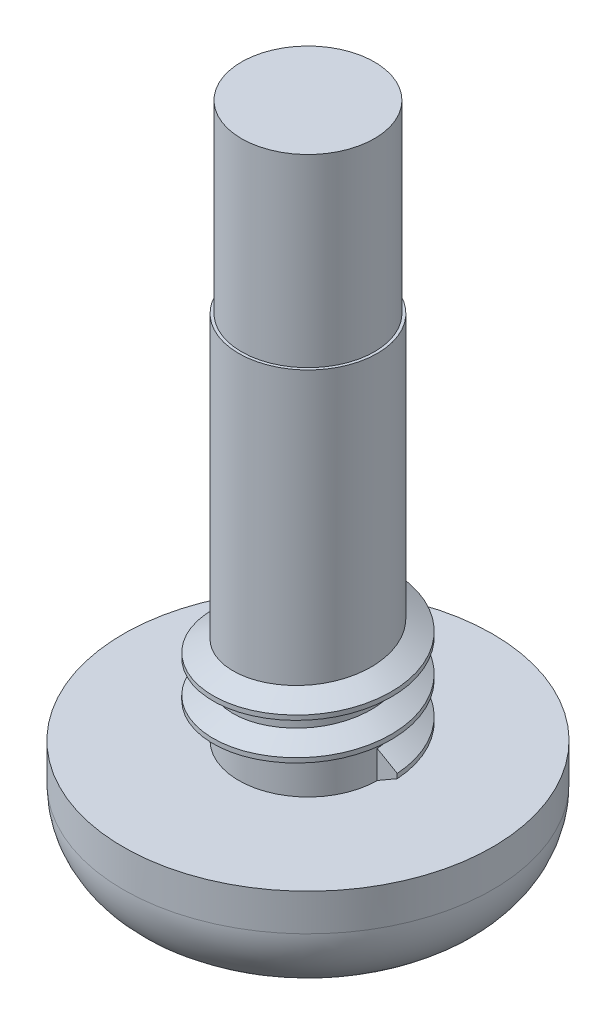
SolidWorks part; units mm, degrees
ref_plane "Front Plane" through (0, 0, 0) normal (0, 0, 1) x (1, 0, 0)
ref_plane "Top Plane" through (0, 0, 0) normal (0, 1, 0) x (1, 0, 0)
ref_plane "Right Plane" through (0, 0, 0) normal (1, 0, 0) x (0, 0, -1)
sketch "Sketch2" plane through (0, 0, 0) normal (0, 1, 0) x (1, 0, 0)
  circle A0 centre (0, 0) radius 6.35
  dimension "D1" = 12.7
extrude "Boss-Extrude1" add sketch "Sketch2" along normal blind 3.81
sketch "Sketch3" plane through (0, 3.81, 0) normal (0, 1, 0) x (1, 0, 0)
  circle A0 centre (0, 0) radius 2.3825
  dimension "D1" = 4.765
extrude "Boss-Extrude2" add sketch "Sketch3" along normal blind 19.0703
thread "Thread2" pitch 1.27 method extrude profile "Thread Profile2" start angle 0, offset 0, length 3.175, pitch 1.27, diameter 4.765
ref_plane "Plane2" through (2.3825, 3.81, 0) normal (0, 0, 1) x (1, 0, 0)
sketch "Thread Profile2" plane through (2.3825, 3.81, 0) normal (0, 0, 1) x (1, 0, 0)
  line L0 (0, 0) -> (0, 1.27) construction
  line L1 (0, 0) -> (0.6874, 0.3969)
  line L2 (0.6874, 0.3969) -> (0.6874, 0.5556)
  line L3 (0.6874, 0.5556) -> (0, 0.9525)
  line L4 (0.6874, 0.4762) -> (0, 0.4762) construction
  line L11 (0, 0) -> (0, 0.9525)
  point P2 (0, 0)
  dimension "Pitch" = 1.27
  dimension "Profile_Angle" = 60
  dimension "Profile_Land" = 0.1588
  dimension "Profile_Height" = 0.6874
sketch "Sketch4" plane through (0, 22.8803, 0) normal (0, 1, 0) x (1, 0, 0)
  circle A0 centre (0, 0) radius 2.286
  dimension "D1" = 4.572
extrude "Cut-Extrude1" cut sketch "Sketch4" against normal blind 6.35 flip side to cut
fillet "Fillet1" radius 2.54 1 edges at (0, 0, 6.35)
